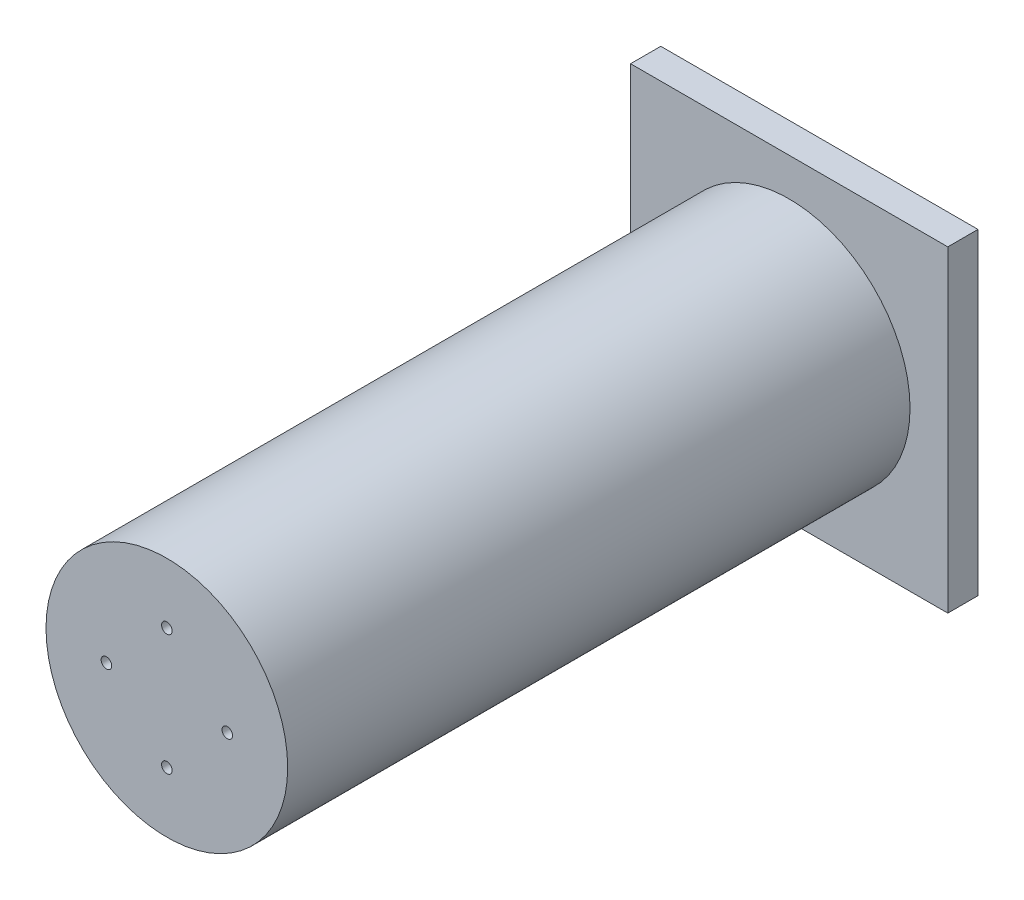
SolidWorks part; units mm, degrees
ref_plane "Alzado" through (0, 0, 0) normal (0, 0, 1) x (1, 0, 0)
ref_plane "Planta" through (0, 0, 0) normal (0, 1, 0) x (1, 0, 0)
ref_plane "Vista lateral" through (0, 0, 0) normal (1, 0, 0) x (0, 0, -1)
sketch "Croquis1" plane through (0, 0, 0) normal (0, 0, 1) x (1, 0, 0)
  line L1 (-117.2917, 97.7627) -> (131.4683, 97.7627)
  line L2 (-117.2917, 97.7627) -> (-117.2917, -97.2373)
  line L3 (-117.2917, -97.2373) -> (131.4683, -97.2373)
  line L4 (131.4683, 97.7627) -> (131.4683, -97.2373)
  dimension "D1" = 248.76
  dimension "D2" = 195
extrude "Saliente-Extruir1" add sketch "Croquis1" along normal blind 5
sketch "Croquis2" plane through (0, 0, 5) normal (0, 0, 1) x (1, 0, 0)
  line L0 (-117.2917, 0.2627) -> (131.4683, 0.2627) construction
  line L1 (-117.2917, 97.7627) -> (-117.2917, -97.2373) construction
  line L2 (131.4683, -97.2373) -> (131.4683, 97.7627) construction
  line L3 (-117.2917, -97.2373) -> (-69.2917, -97.2373)
  line L4 (-117.2917, -97.2373) -> (131.4683, -97.2373) construction
  line L5 (-69.2917, -97.2373) -> (-69.2917, -67.2373)
  line L6 (-69.2917, -67.2373) -> (-117.2917, -67.2373)
  line L7 (-117.2917, -67.2373) -> (-117.2917, -97.2373)
  line L8 (131.4683, 67.7627) -> (101.4683, 67.7627)
  line L9 (131.4683, -97.2373) -> (101.4683, -97.2373)
  line L10 (131.4683, -97.2373) -> (131.4683, -67.2373)
  line L11 (131.4683, -67.2373) -> (101.4683, -67.2373)
  line L12 (101.4683, -97.2373) -> (101.4683, -67.2373)
  line L13 (101.4683, 97.7627) -> (101.4683, 67.7627)
  line L14 (131.4683, 97.7627) -> (101.4683, 97.7627)
  line L15 (131.4683, 97.7627) -> (131.4683, 67.7627)
  line L16 (-69.2917, 67.7627) -> (-117.2917, 67.7627)
  line L17 (-69.2917, 97.7627) -> (-69.2917, 67.7627)
  line L18 (-117.2917, 97.7627) -> (-69.2917, 97.7627)
  line L19 (-117.2917, 67.7627) -> (-117.2917, 97.7627)
  dimension "D1" = 48
  dimension "D2" = 30
  dimension "D3" = 30
  dimension "D4" = 30
extrude "Cortar-Extruir1" cut sketch "Croquis2" against normal blind 2
sketch "Croquis3" plane through (0, 0, 5) normal (0, 0, 1) x (1, 0, 0)
  line L0 (-69.2917, 97.7627) -> (-117.2917, 97.7627) construction
  line L1 (116.4683, 83.7627) -> (116.4683, 67.7627) construction
  line L3 (116.4683, -83.2373) -> (116.4683, -67.2373) construction
  line L5 (131.4683, -67.2373) -> (101.4683, -67.2373) construction
  line L6 (101.4683, 67.7627) -> (131.4683, 67.7627) construction
  line L7 (-93.2917, 83.7627) -> (-93.2917, 67.7627) construction
  line L8 (-117.2917, 67.7627) -> (-69.2917, 67.7627) construction
  line L9 (-93.2917, -83.2373) -> (-93.2917, -67.2373) construction
  line L10 (-69.2917, -67.2373) -> (-117.2917, -67.2373) construction
  circle A0 centre (-93.2917, 83.7627) radius 2.375
  circle A1 centre (-93.2917, -83.2373) radius 2.375
  circle A2 centre (116.4683, 83.7627) radius 2.375
  circle A3 centre (116.4683, -83.2373) radius 2.375
  dimension "D2" = 4.75
  dimension "D3" = 4.75
  dimension "D5" = 4.75
  dimension "D6" = 4.75
  dimension "D1" = 14
  dimension "D4" = 14
  dimension "D7" = 209.76
  dimension "D8" = 16
  dimension "D9" = 16
extrude "Cortar-Extruir2" cut sketch "Croquis3" against normal blind 10
sketch "Croquis4" plane through (0, 0, 0) normal (0, 0, -1) x (-1, 0, 0)
  line L7 (-131.4683, 97.7627) -> (117.2917, 97.7627) construction
  line L9 (117.2917, 97.7627) -> (117.2917, -97.2373) construction
  circle A0 centre (55.1017, 0.2627) radius 40
  dimension "D3" = 80
  dimension "D1" = 62.19
  dimension "D2" = 97.5
extrude "Saliente-Extruir2" add sketch "Croquis4" along normal blind 206 contours A0
sketch "Croquis5" plane through (0, 0, 0) normal (0, 0, -1) x (-1, 0, 0)
  line L0 (-131.4683, 0.2627) -> (117.2917, 0.2627) construction
  line L1 (-131.4683, -97.2373) -> (-131.4683, 97.7627) construction
  line L2 (117.2917, 97.7627) -> (117.2917, -97.2373) construction
  circle A0 centre (-76.9683, 0.2627) radius 12.5
  dimension "D1" = 25
  dimension "D2" = 54.5
extrude "Cortar-Extruir3" cut sketch "Croquis5" against normal blind 10
sketch "Croquis6" plane through (0, 0, 0) normal (0, 0, -1) x (-1, 0, 0)
  line L0 (-131.4683, 97.7627) -> (117.2917, 97.7627) construction
  line L1 (-7.0883, 97.7627) -> (-7.0883, -97.2373)
  line L2 (117.2917, -97.2373) -> (-131.4683, -97.2373) construction
  line L3 (-7.0883, 97.7627) -> (117.2917, 97.7627)
  line L4 (117.2917, 97.7627) -> (117.2917, -97.2373)
  line L5 (117.2917, -97.2373) -> (-7.0883, -97.2373)
  line L6 (-131.4683, 0.2627) -> (56.0317, 0.2627)
  line L7 (-131.4683, -97.2373) -> (-131.4683, 97.7627) construction
  circle A1 centre (56.0317, 0.2627) radius 100
  dimension "D1" = 200
  dimension "D2" = 187.5
sketch "Croquis9" plane through (0, 97.7627, 0) normal (0, 1, 0) x (1, 0, 0)
  line L0 (7.0883, 0) -> (7.0883, -5)
  line L1 (131.4683, 0) -> (-117.2917, 0) construction
  line L2 (101.4683, -5) -> (-69.2917, -5) construction
ref_plane "Plano3" through (7.0883, 0, 0) normal (1, 0, 0) x (0, 0, -1)
sketch "Croquis12" plane through (7.0883, 0, 0) normal (1, 0, 0) x (0, 0, -1)
  line L0 (0, 97.7627) -> (0, 67.7627)
  line L1 (0, 67.7627) -> (12, 67.7627)
  line L2 (12, 67.7627) -> (12, 97.7627)
  line L3 (12, 97.7627) -> (0, 97.7627)
  line L4 (0, -97.2373) -> (12, -97.2373)
  line L5 (12, -97.2373) -> (12, -67.2373)
  line L6 (12, -67.2373) -> (0, -67.2373)
  line L7 (0, -67.2373) -> (0, -97.2373)
  dimension "D1" = 30
  dimension "D2" = 12
  dimension "D3" = 30
  dimension "D4" = 12
extrude "Saliente-Extruir3" add sketch "Croquis12" along normal mid plane 8
fillet "Redondeo1" radius 10 2 edges at (7.0883, -67.2373, 0) (7.0883, 67.7627, 0)
fillet "Redondeo2" radius 10 2 edges at (7.0883, 67.7627, -12) (7.0883, -67.2373, -12)
fillet "Redondeo3" radius 10 2 edges at (7.0883, -97.2373, -12) (7.0883, 97.7627, -12)
sketch "Croquis13" plane through (11.0883, 0, 0) normal (1, 0, 0) x (0, 0, -1)
  line L0 (-5, 0.2627) -> (206, 0.2627) construction
  line L1 (-5, -67.2373) -> (-5, 67.7627) construction
  line L2 (206, -39.7373) -> (206, 40.2627) construction
  line L3 (6, 87.7627) -> (12, 87.7627) construction
  line L4 (6, 87.7627) -> (6, 77.7627) construction
  circle A0 centre (6, 87.7627) radius 1.625
  circle A1 centre (6, 77.7627) radius 1.625
  circle A2 centre (6, -77.2373) radius 1.625
  circle A3 centre (6, -87.2373) radius 1.625
  dimension "D3" = 3.25
  dimension "D4" = 3.25
  dimension "D1" = 6
extrude "Cortar-Extruir5" cut sketch "Croquis13" against normal through all both and the other way through all
sketch "Croquis14" plane through (0, 0, 0) normal (0, 0, -1) x (-1, 0, 0)
  line L0 (-7.0883, 97.7627) -> (-7.0883, -97.2373)
  line L1 (-7.0883, 97.7627) -> (117.2917, 97.7627)
  line L2 (117.2917, 97.7627) -> (117.2917, -97.2373)
  line L3 (117.2917, -97.2373) -> (-7.0883, -97.2373)
sketch "Croquis15" plane through (0, 0, 5) normal (0, 0, 1) x (1, 0, 0)
  line L0 (111.4683, 67.7627) -> (131.4683, 67.7627)
  line L1 (111.4683, 67.7627) -> (111.4683, 60.0127)
  line L2 (131.4683, -67.2373) -> (101.4683, -67.2373) construction
  line L3 (111.4683, -67.2373) -> (111.4683, -59.4873)
  line L4 (111.4683, -59.4873) -> (125.2183, -59.4873)
  line L5 (125.2183, -59.4873) -> (125.2183, 60.0127)
  line L6 (111.4683, 60.0127) -> (125.2183, 60.0127)
  line L7 (111.4683, -67.2373) -> (131.4683, -67.2373)
  line L10 (131.4683, -67.2373) -> (131.4683, 67.7627)
  dimension "D1" = 119.5
  dimension "D2" = 7.75
  dimension "D3" = 13.75
extrude "Cortar-Extruir7" cut sketch "Croquis15" against normal blind 2
sketch "Croquis16" plane through (0, 0, 5) normal (0, 0, 1) x (1, 0, 0)
  circle A1 centre (-55.1017, 20.2627) radius 1.75
  circle A2 centre (-35.1017, 0.2627) radius 1.75
  circle A3 centre (-55.1017, -19.7373) radius 1.75
  circle A4 centre (-75.1017, 0.2627) radius 1.75
  dimension "D3" = 3.5
  dimension "D4" = 4
extrude "Cortar-Extruir9" cut sketch "Croquis16" against normal blind 20
sketch "Croquis20" plane through (0, -97.2373, 0) normal (0, -1, 0) x (1, 0, 0)
  line L0 (-117.2917, 10.5315) -> (-117.2917, 0)
  line L1 (-117.2917, 0) -> (3.0883, 0)
  line L2 (3.0883, 0) -> (3.0883, -12)
  line L3 (3.0883, -12) -> (11.0883, -12)
  line L4 (11.0883, -12) -> (11.0883, 0)
  line L5 (11.0883, 0) -> (131.4683, 0)
  line L6 (131.4683, 0) -> (131.4683, 10.5315)
  line L7 (131.4683, 10.5315) -> (-117.2917, 10.5315)
extrude "Cortar-Extruir17" cut sketch "Croquis20" against normal through all both and the other way through all
sketch "Croquis21" plane through (0, 0, -206) normal (0, 0, -1) x (-1, 0, 0)
  line L1 (2.6017, -52.2373) -> (107.6017, -52.2373)
  line L2 (2.6017, -52.2373) -> (2.6017, 52.7627)
  line L3 (2.6017, 52.7627) -> (107.6017, 52.7627)
  line L4 (107.6017, -52.2373) -> (107.6017, 52.7627)
  line L5 (2.6017, -52.2373) -> (107.6017, 52.7627) construction
  line L6 (2.6017, 52.7627) -> (107.6017, -52.2373) construction
  point P0 (55.1017, 0.2627)
  dimension "D1" = 105
  dimension "D2" = 105
extrude "Saliente-Extruir4" add sketch "Croquis21" along normal blind 10
